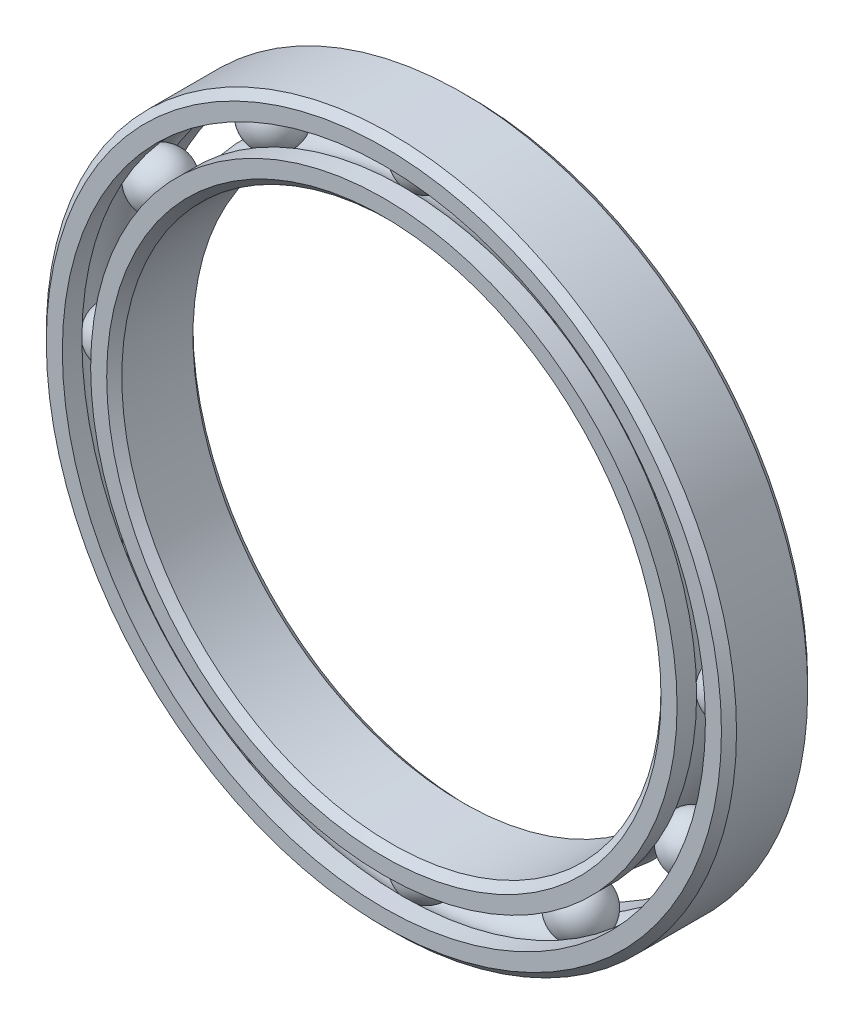
SolidWorks part; units mm, degrees
ref_plane "Front Plane" through (0, 0, 0) normal (0, 0, 1) x (1, 0, 0)
ref_plane "Top Plane" through (0, 0, 0) normal (0, 1, 0) x (1, 0, 0)
ref_plane "Right Plane" through (0, 0, 0) normal (1, 0, 0) x (0, 0, -1)
sketch "Sketch1" plane through (0, 0, 0) normal (1, 0, 0) x (0, 0, -1)
  line L0 (-2, 0) -> (2, 0) construction
  line L1 (0, 16) -> (0, -16) construction
  line L2 (1.65, 16) -> (-1.65, 16)
  line L3 (-1.65, 16) -> (-2, 15.65)
  line L4 (-2, 15.65) -> (-2, 14.9063)
  line L5 (-2, 14.9063) -> (-1.094, 14.9063)
  line L6 (2, 14.9063) -> (1.094, 14.9063)
  line L7 (2, 15.65) -> (2, 14.9063)
  line L8 (1.65, 16) -> (2, 15.65)
  line L9 (0, 16) -> (0, 14.25) construction
  line L10 (0, 14.25) -> (0, 12.5) construction
  arc A0 (-1.094, 14.9063) -> (1.094, 14.9063) centre (0, 14.25) cw
  point P14 (0, 12.5)
  point P15 (0.872, 15.1813)
  dimension "Width" = 4
  dimension "OD" = 32
  dimension "D1" = 45
  dimension "D2" = 0.35
  dimension "Shaft Dia" = 25
revolve "Revolve1" add sketch "Sketch1" angle 360 about L0
sketch "Sketch3" plane through (0, 0, 0) normal (1, 0, 0) x (0, 0, -1)
  line L0 (-2, 13.5937) -> (-1.094, 13.5937)
  line L1 (0, 16) -> (0, -16) construction
  line L2 (-2, 15.65) -> (-2, 14.9063) construction
  line L3 (-2, 13.5937) -> (-2, 12.85)
  line L4 (-1.65, 16) -> (-2, 15.65) construction
  line L5 (-2, 12.85) -> (-1.65, 12.5)
  line L6 (-1.65, 12.5) -> (1.65, 12.5)
  line L7 (1.65, 16) -> (1.65, -16) construction
  line L8 (1.65, 12.5) -> (2, 12.85)
  line L9 (2, -15.65) -> (2, 15.65) construction
  line L10 (2, 12.85) -> (2, 13.5937)
  line L11 (2, 13.5937) -> (1.094, 13.5937)
  line L13 (1.65, 16) -> (2, 15.65) construction
  arc A0 (1.094, 14.9063) -> (-1.094, 14.9063) centre (0, 14.25) ccw construction
  arc A1 (1.094, 13.5937) -> (-1.094, 13.5937) centre (0, 14.25) cw
revolve "Revolve3" add sketch "Sketch3" angle 360 about L0
sketch "Sketch4" plane through (0, 0, 0) normal (1, 0, 0) x (0, 0, -1)
  line L0 (-1.2758, 14.25) -> (1.2758, 14.25)
  arc A2 (-1.2758, 14.25) -> (1.2758, 14.25) centre (0, 14.25) cw
  arc A3 (1.094, 14.9063) -> (-1.094, 14.9063) centre (0, 14.25) ccw construction
revolve "Revolve4" add sketch "Sketch4" angle 360 about L0
ref_axis "Axis1" through (0, 0, -2) along (0, 0, 1)
pattern_circular "CirPattern1" count 12 over 360 about axis through (0, 0, -2) along (0, 0, 1) of bodies 104
sketch "Sketch5" plane through (0, 0, 0) normal (1, 0, 0) x (0, 0, -1)
  line L0 (-2, 14.9063) -> (-1.094, 14.9063) construction
  line L1 (-1.825, 14.9063) -> (-1.2758, 14.9063)
  line L2 (-1.825, 14.9063) -> (-1.825, 13.5937)
  line L3 (-1.825, 13.5937) -> (-1.2758, 13.5937)
  line L4 (-1.2758, 14.9063) -> (-1.2758, 13.5937)
  line L5 (-2, 13.5937) -> (-1.094, 13.5937) construction
  line L6 (2, 14.9063) -> (1.094, 14.9063) construction
  line L7 (1.825, 14.9063) -> (1.2758, 14.9063)
  line L8 (1.825, 14.9063) -> (1.825, 13.5937)
  line L9 (1.825, 13.5937) -> (1.2758, 13.5937)
  line L10 (1.2758, 14.9063) -> (1.2758, 13.5937)
  line L11 (2, 13.5937) -> (1.094, 13.5937) construction
  line L12 (-1.65, 16) -> (-2, 15.65) construction
  point P18 (-1.825, 15.825)
equation "\"D2@Sketch1\" = \"Width@Sketch1\"*.05"
equation "\"D2@CirPattern1\" = 360/\"Balls@CirPattern1\""
